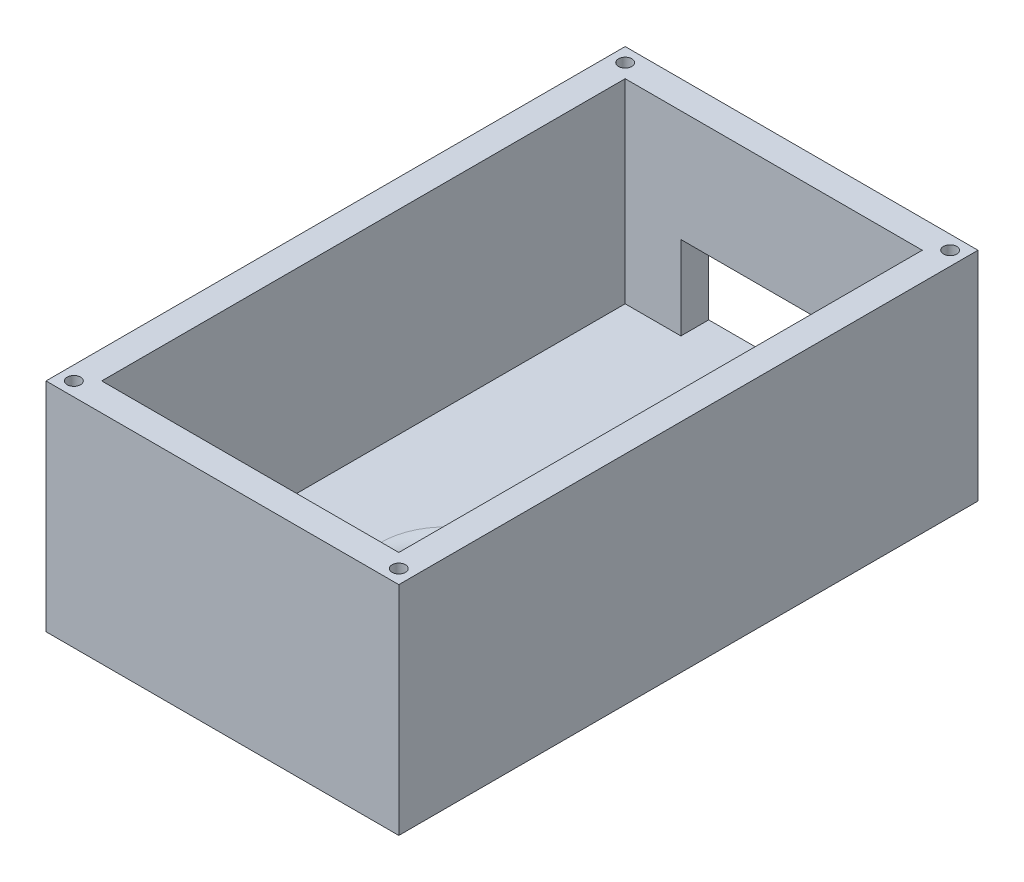
SolidWorks part; units mm, degrees
ref_plane "Piano frontale" through (0, 0, 0) normal (0, 0, 1) x (1, 0, 0)
ref_plane "Piano superiore" through (0, 0, 0) normal (0, 1, 0) x (1, 0, 0)
ref_plane "Piano destro" through (0, 0, 0) normal (1, 0, 0) x (0, 0, -1)
sketch "Schizzo1" plane through (0, 0, 0) normal (0, 1, 0) x (1, 0, 0)
  line L1 (2.4905, 3.4245) -> (65.8305, 3.4245)
  line L2 (2.4905, 3.4245) -> (2.4905, 107.4045)
  line L3 (2.4905, 107.4045) -> (65.8305, 107.4045)
  line L4 (65.8305, 3.4245) -> (65.8305, 107.4045)
  dimension "D1" = 103.98
  dimension "D2" = 63.34
extrude "Estrusione-Estrusione1" add sketch "Schizzo1" along normal blind 4
sketch "Schizzo2" plane through (0, 4, 0) normal (0, 1, 0) x (1, 0, 0)
  line L0 (2.4905, 107.4045) -> (2.4905, 3.4245) construction
  line L1 (2.4905, 107.4045) -> (65.8305, 107.4045)
  line L2 (2.4905, 107.4045) -> (2.4905, 3.4245)
  line L3 (2.4905, 3.4245) -> (65.8305, 3.4245)
  line L4 (65.8305, 107.4045) -> (65.8305, 3.4245)
  line L5 (7.4905, 102.4045) -> (7.4905, 8.4245)
  line L6 (7.4905, 8.4245) -> (60.8305, 8.4245)
  line L7 (60.8305, 102.4045) -> (60.8305, 8.4245)
  line L8 (7.4905, 102.4045) -> (60.8305, 102.4045)
  dimension "D1" = 5
extrude "Estrusione-Estrusione2" add sketch "Schizzo2" along normal blind 35
hole_wizard "Foro per Vite M2-1" positions "Schizzo3" profile "Schizzo4" hole size "M2" standard "Ansi Metric" end condition through all
sketch "Schizzo3" plane through (0, 39, 0) normal (0, 1, 0) x (1, 0, 0)
  line L0 (2.4905, 107.4045) -> (2.4905, 3.4245) construction
  line L1 (65.8305, 107.4045) -> (2.4905, 107.4045) construction
  line L2 (65.8305, 3.4245) -> (65.8305, 107.4045) construction
  line L3 (2.4905, 3.4245) -> (65.8305, 3.4245) construction
  point P0 (4.9905, 104.9045)
  point P2 (63.3305, 104.9045)
  point P4 (63.3305, 5.9245)
  point P6 (4.9905, 5.9245)
  dimension "D1" = 2.5
  dimension "D2" = 2.5
  dimension "D3" = 2.5
  dimension "D4" = 2.5
  dimension "D5" = 2.5
  dimension "D6" = 2.5
  dimension "D7" = 2.5
  dimension "D8" = 2.5
sketch "Schizzo4" plane through (4.9905, 39, -104.9045) normal (1, 0, 0) x (0, 0, 1)
  line L0 (0, 0) -> (0, 39)
  line L1 (0, 39) -> (1.2, 39)
  line L2 (1.2, 39) -> (1.2, 0)
  line L5 (1.2, 0) -> (0, 0)
  line L11 (0, -6.35) -> (0, 107.95) construction
  dimension "Thru Hole Dia." = 2.4
  dimension "Thru Hole Depth" = 39
sketch "Schizzo5" plane through (0, 0, -102.4045) normal (0, 0, 1) x (1, 0, 0)
  line L0 (2.4905, 0) -> (65.8305, 0) construction
  line L1 (17.4905, 4) -> (50.8305, 4)
  line L2 (17.4905, 4) -> (17.4905, 19)
  line L3 (17.4905, 19) -> (50.8305, 19)
  line L4 (50.8305, 4) -> (50.8305, 19)
  line L5 (2.4905, 39) -> (2.4905, 0) construction
  line L6 (65.8305, 39) -> (65.8305, 0) construction
  dimension "D1" = 4
  dimension "D2" = 15
  dimension "D3" = 15
  dimension "D4" = 15
extrude "Taglio-Estrusione1" cut sketch "Schizzo5" against normal through all
sketch "Schizzo6" plane through (0, 0, 0) normal (0, -1, 0) x (-1, 0, 0)
  line L0 (-2.4905, 3.4245) -> (-65.8305, 3.4245) construction
  line L1 (-65.8305, 3.4245) -> (-65.8305, 107.4045) construction
  line L4 (-31.1605, 33.8198) -> (-31.1605, 20.4245)
  line L5 (-33.1605, 18.4245) -> (-35.1605, 18.4245)
  line L6 (-37.1605, 33.8198) -> (-37.1605, 20.4245)
  arc A0 (-29.3605, 37.6617) -> (-38.9605, 37.6617) centre (-34.1605, 43.4245) ccw
  arc A1 (-37.1605, 20.4245) -> (-35.1605, 18.4245) centre (-35.1605, 20.4245) ccw
  arc A2 (-31.1605, 20.4245) -> (-33.1605, 18.4245) centre (-33.1605, 20.4245) cw
  arc A3 (-29.3605, 37.6617) -> (-31.1605, 33.8198) centre (-26.1605, 33.8198) ccw
  arc A4 (-38.9605, 37.6617) -> (-37.1605, 33.8198) centre (-42.1605, 33.8198) cw
  point P10 (-34.1605, 18.4245)
  point P13 (-37.1605, 18.4245)
  dimension "D1" = 15
  dimension "D3" = 31.67
  dimension "D8" = 2
  dimension "D9" = 2
  dimension "D4" = 5
  dimension "D2" = 40
  dimension "D5" = 31.67
extrude "Taglio-Estrusione2" cut sketch "Schizzo6" against normal through all
fillet "Raccordo1" radius 4 8 edges at (30.6882, 4, -35.9411) (31.1605, 4, -27.1221) (31.7463, 4, -19.0103) (34.1605, 4, -18.4245) (36.5748, 4, -19.0103) (37.1605, 4, -27.1221) (37.6328, 4, -35.9411) (34.1605, 4, -50.9245)
